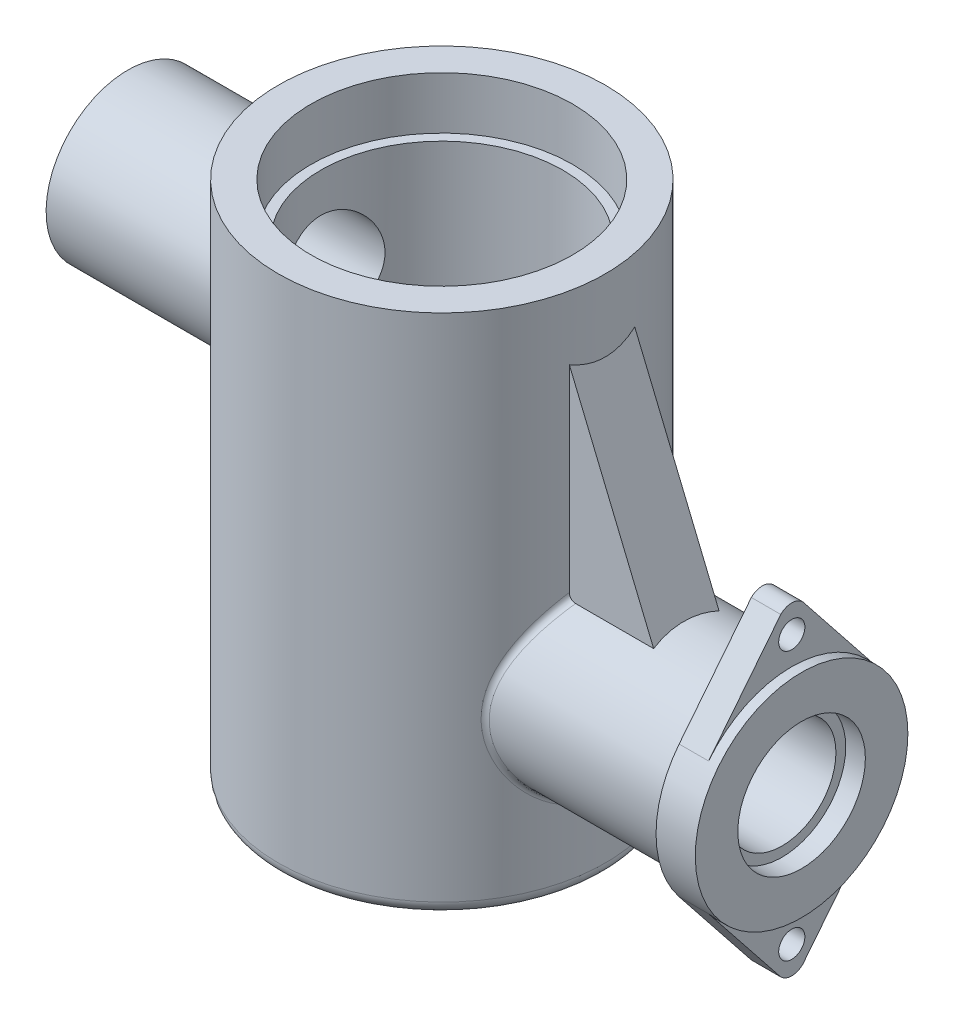
SolidWorks part; units mm, degrees
ref_plane "Front Plane" through (0, 0, 0) normal (0, 0, 1) x (1, 0, 0)
ref_plane "Top Plane" through (0, 0, 0) normal (0, 1, 0) x (1, 0, 0)
ref_plane "Right Plane" through (0, 0, 0) normal (1, 0, 0) x (0, 0, -1)
sketch "Sketch1" plane through (0, 0, 0) normal (0, 0, 1) x (1, 0, 0)
  line L0 (0, 0) -> (0, 34.8158) construction
  line L1 (9.5, 0) -> (16, 0)
  line L2 (16, 0) -> (16, 3)
  line L3 (18, 5) -> (23, 5)
  line L4 (25, 7) -> (25, 85)
  line L5 (25, 85) -> (20, 85)
  line L6 (20, 85) -> (20, 77)
  line L7 (20, 77) -> (18.5, 77)
  line L8 (18.5, 77) -> (18.5, 54)
  line L9 (17.5, 53) -> (14.5, 53)
  line L10 (14.5, 53) -> (14.5, 49.5)
  line L11 (14.5, 49.5) -> (9.5, 49.5)
  line L12 (9.5, 49.5) -> (9.5, 46.5)
  line L13 (9.5, 46.5) -> (17.5, 46.5)
  line L14 (18.5, 45.5) -> (18.5, 13)
  line L15 (16.5, 11) -> (9.5, 11)
  line L16 (9.5, 11) -> (9.5, 0)
  arc A0 (16, 3) -> (18, 5) centre (18, 3) cw
  arc A1 (23, 5) -> (25, 7) centre (23, 7) ccw
  arc A2 (18.5, 54) -> (17.5, 53) centre (17.5, 54) cw
  arc A3 (17.5, 46.5) -> (18.5, 45.5) centre (17.5, 45.5) cw
  arc A4 (18.5, 13) -> (16.5, 11) centre (16.5, 13) cw
  point P9 (16, 5)
  point P13 (25, 5)
  point P21 (18.5, 53)
  point P29 (18.5, 46.5)
  point P33 (18.5, 11)
  dimension "D5" = 2
  dimension "D7" = 2
  dimension "D13" = 1
  dimension "D19" = 1
  dimension "D21" = 2
  dimension "D1" = 9.5
  dimension "D2" = 6.5
  dimension "D3" = 5
  dimension "D4" = 9
  dimension "D6" = 80
  dimension "D8" = 5
  dimension "D9" = 8
  dimension "D10" = 1.5
  dimension "D11" = 24
  dimension "D12" = 4
  dimension "D14" = 3.5
  dimension "D15" = 5
  dimension "D16" = 3
  dimension "D17" = 9
  dimension "D18" = 35.5
  dimension "D20" = 9
revolve "Revolve1" add sketch "Sketch1" angle 360 about L0
ref_plane "Plane1" through (49, 0, 0) normal (1, 0, 0) x (0, 0, -1)
sketch "Sketch2" plane through (49, 0, 0) normal (1, 0, 0) x (0, 0, -1)
  line L0 (13.5805, 21.9699) -> (1.6796, 7)
  line L1 (25, 7) -> (-25, 7) construction
  line L2 (0, 0) -> (0, 74.6071) construction
  line L3 (-13.5805, 21.9699) -> (-1.6796, 7)
  line L4 (47.2379, 31) -> (-57.453, 31) construction
  line L5 (-13.5805, 40.0301) -> (-1.6796, 55)
  line L6 (13.5805, 40.0301) -> (1.6796, 55)
  circle A0 centre (0, 31) radius 8.25
  circle A1 centre (0, 31) radius 9.75
  circle A2 centre (0, 31) radius 16.25
  circle A3 centre (0, 51.5) radius 2
  circle A4 centre (0, 10.5) radius 2
  arc A5 (1.6796, 7) -> (-1.6796, 7) centre (0, 8.6796) cw
  arc A6 (1.6796, 55) -> (-1.6796, 55) centre (0, 53.3204) ccw
  dimension "D2" = 16.5
  dimension "D3" = 19.5
  dimension "D4" = 32.5
  dimension "D6" = 4
  dimension "D8" = 4
  dimension "D1" = 31
  dimension "D5" = 20.5
  dimension "D7" = 20.5
extrude "Boss-Extrude1" add sketch "Sketch2" along normal blind 4.5 separate body contours A5 L0 A2 L3 A4 | L6 A6 L5 A2 A3 region at (49, 12.7354, 0) region at (49, 49.2646, 0)
extrude "Boss-Extrude2" add sketch "Sketch2<3>" along normal blind 6 contours A2 A1 region at (49, 15.2096, 0)
sketch "Sketch2<3>" plane through (49, 0, 0) normal (1, 0, 0) x (0, 0, -1) same geometry as "Sketch2"
extrude "Boss-Extrude3" add sketch "Sketch2<4>" along normal blind 6 contours A1 A0 | A0 region at (49, 31, 0) region at (49, 31, 9.4742)
sketch "Sketch2<4>" plane through (49, 0, 0) normal (1, 0, 0) x (0, 0, -1) same geometry as "Sketch2"
sketch "Sketch3" plane through (55, 0, 0) normal (1, 0, 0) x (0, 0, -1)
  line L0 (-13.5805, 21.9699) -> (-1.6796, 7) construction
  line L1 (13.5805, 21.9699) -> (1.6796, 7) construction
  line L2 (-13.5805, 40.0301) -> (-1.6796, 55) construction
  line L3 (13.5805, 40.0301) -> (1.6796, 55) construction
  line L4 (-13.5805, 21.9699) -> (-1.6796, 7)
  line L5 (13.5805, 21.9699) -> (1.6796, 7)
  line L6 (-13.5805, 40.0301) -> (-1.6796, 55)
  line L7 (13.5805, 40.0301) -> (1.6796, 55)
  arc A0 (-1.6796, 7) -> (1.6796, 7) centre (0, 8.6796) ccw construction
  circle A1 centre (0, 10.5) radius 2
  circle A2 centre (0, 10.5) radius 2
  circle A3 centre (0, 51.5) radius 2
  circle A4 centre (0, 51.5) radius 2
  circle A5 centre (0, 31) radius 16.25
  circle A6 centre (0, 31) radius 16.25
  circle A7 centre (0, 31) radius 9.75
  circle A8 centre (0, 31) radius 9.75
  circle A9 centre (0, 31) radius 8.25
  circle A10 centre (0, 31) radius 8.25
  arc A11 (1.6796, 55) -> (-1.6796, 55) centre (0, 53.3204) ccw construction
  arc A12 (-1.6796, 7) -> (1.6796, 7) centre (0, 8.6796) ccw
  arc A13 (1.6796, 55) -> (-1.6796, 55) centre (0, 53.3204) ccw
  dimension "D1" = 0
  dimension "D2" = 0
  dimension "D3" = 0
  dimension "D4" = 0
  dimension "D5" = 0
extrude "Cut-Extrude1" cut sketch "Sketch3" against normal blind 3 contours A8 A10 region at (55, 31, 9.4742)
extrude "Cut-Extrude2" cut sketch "Sketch3<3>" against normal blind 6 contours A10 region at (55, 31, 0)
sketch "Sketch3<3>" plane through (55, 0, 0) normal (1, 0, 0) x (0, 0, -1) same geometry as "Sketch3"
sketch "Sketch5" plane through (49, 0, 0) normal (-1, 0, 0) x (0, 0, 1)
  circle A0 centre (0, 31) radius 14
  dimension "D1" = 28
extrude "Boss-Extrude4" add sketch "Sketch5" along normal up to next
sketch "Sketch6" plane through (49, 0, 0) normal (1, 0, 0) x (0, 0, -1)
  circle A0 centre (0, 31) radius 8.25 construction
  circle A1 centre (0, 31) radius 8.25
extrude "Cut-Extrude3" cut sketch "Sketch6" against normal up to next
fillet "Fillet1" radius 1 2 edges at (20.7431, 29.8705, 13.9544) (49, 31, -14)
ref_plane "Plane2" through (-48, 0, 0) normal (1, 0, 0) x (0, 0, -1)
sketch "Sketch7" plane through (-48, 0, 0) normal (1, 0, 0) x (0, 0, -1)
  circle A0 centre (0, 63) radius 8
  circle A1 centre (0, 63) radius 12.5
  dimension "D2" = 16
  dimension "D3" = 25
  dimension "D1" = 63
extrude "Boss-Extrude5" add sketch "Sketch7" along normal up to next
sketch "Sketch8" plane through (-48, 0, 0) normal (-1, 0, 0) x (0, 0, 1)
  circle A0 centre (0, 63) radius 8 construction
  circle A1 centre (0, 63) radius 8
extrude "Cut-Extrude4" cut sketch "Sketch8" against normal up to next
fillet "Fillet2" radius 2 1 edges at (-21.6918, 61.6651, -12.4285)
sketch "Sketch9" plane through (0, 0, 0) normal (0, 0, 1) x (1, 0, 0)
  line L0 (25, 74) -> (37, 45)
  line L1 (25, 46) -> (25, 85) construction
  line L2 (48, 45) -> (26, 45) construction
  dimension "D1" = 74
  dimension "D2" = 37
rib "Rib1" sketch "Sketch9" sketch "Sketch9" thickness 10 extrusion direction parallel to sketch draft on no parameters "D1"=10
